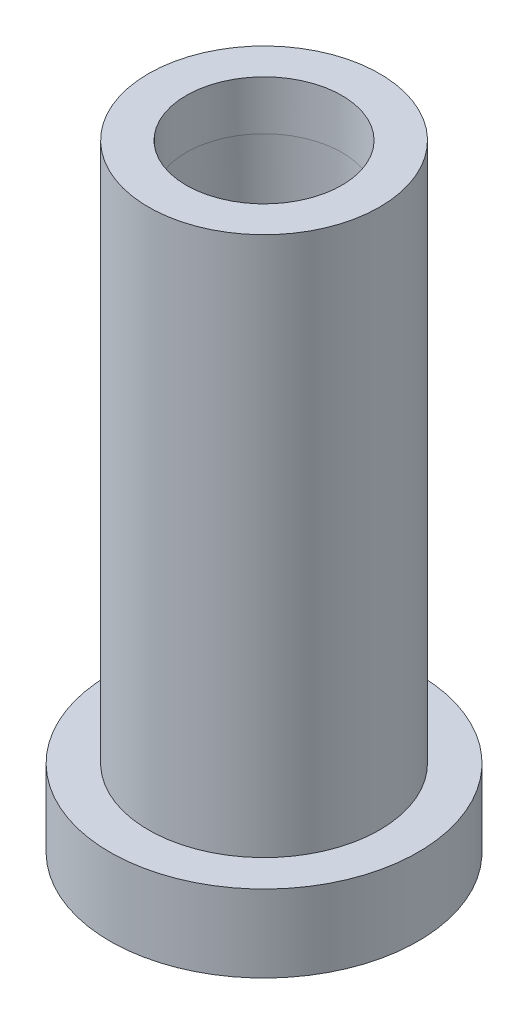
SolidWorks part; units mm, degrees
material "K110"
ref_plane "Front Plane" through (0, 0, 0) normal (0, 0, 1) x (1, 0, 0)
ref_plane "Top Plane" through (0, 0, 0) normal (0, 1, 0) x (1, 0, 0)
ref_plane "Right Plane" through (0, 0, 0) normal (1, 0, 0) x (0, 0, -1)
sketch "Sketch1" plane through (0, 0, 0) normal (0, 0, 1) x (1, 0, 0)
  line L0 (0, 0) -> (10, 0)
  line L1 (10, 0) -> (10, 5)
  line L2 (10, 5) -> (7.5, 5)
  line L3 (7.5, 5) -> (7.5, 40)
  line L4 (7.5, 40) -> (0, 40)
  line L5 (0, 40) -> (0, 0)
  line L6 (0, 45) -> (0, -5) construction
  line L7 (9.9, 0) -> (-9.9, 0) construction
  dimension "D1" = 5
  dimension "D2" = 5
  dimension "D3" = 15
  dimension "D4" = 20
  dimension "D5" = 5
  dimension "D6" = 40
revolve "Revolve1" add sketch "Sketch1" angle 360 about L6
sketch "Sketch2" plane through (0, 40, 0) normal (0, 1, 0) x (1, 0, 0)
  circle A0 centre (0, 0) radius 5.05
  dimension "D1" = 10.1
extrude "Cut-Extrude1" cut sketch "Sketch2" against normal up to next
sketch "Sketch4" plane through (0, 40, 0) normal (0, 1, 0) x (1, 0, 0)
  circle A0 centre (0, 0) radius 5.05 construction
  circle A1 centre (0, 0) radius 5.05
sketch "Sketch3" plane through (0, 0, 0) normal (0, 0, 1) x (1, 0, 0)
  line L0 (5.05, 36.8) -> (6.0136, 0)
  line L1 (5.05, 0) -> (5.05, 40) construction
  line L2 (11, 0) -> (-11, 0) construction
  line L3 (6.0136, 0) -> (5.05, 0)
  line L4 (5.05, 0) -> (5.05, 36.8)
  line L5 (7.5, 40) -> (-7.5, 40) construction
  dimension "D1" = 3.2
  dimension "D2" = 1.5
sweep "Cut-Sweep1" cut profiles "Sketch3" path "Sketch4"
